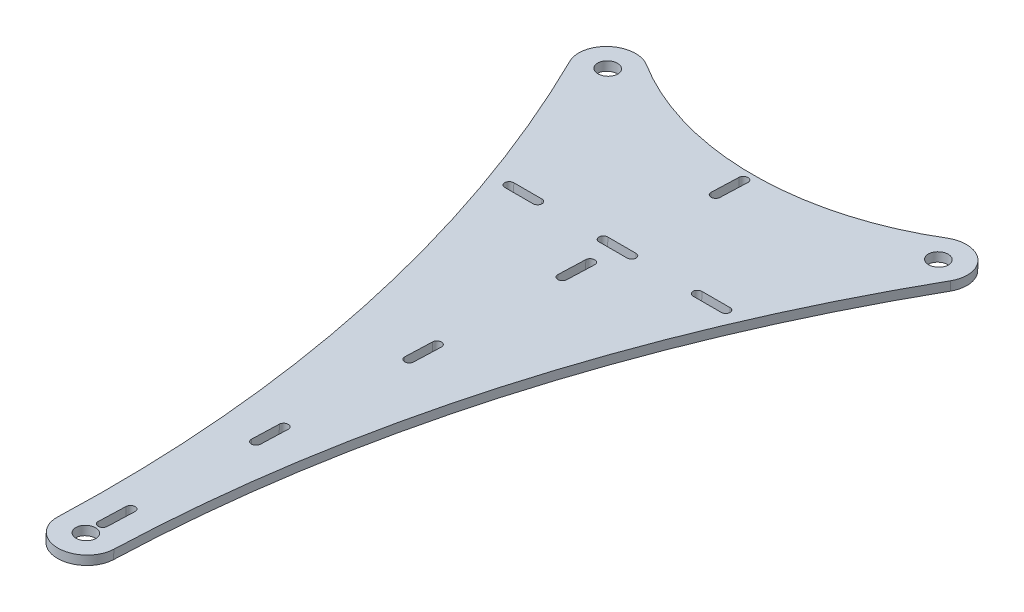
SolidWorks part; units mm, degrees
ref_plane "Front Plane" through (0, 0, 0) normal (0, 0, 1) x (1, 0, 0)
ref_plane "Top Plane" through (0, 0, 0) normal (0, 1, 0) x (1, 0, 0)
ref_plane "Right Plane" through (0, 0, 0) normal (1, 0, 0) x (0, 0, -1)
sketch "Sketch1" plane through (0, 79.1663, -2.7669) normal (0, -0.9994, 0.0349) x (0, -0.0349, -0.9994)
  line L0 (4.8479, 0) -> (-4.8479, 0) construction
  circle A0 centre (-118.8704, 0) radius 3.5
  circle A1 centre (126.4846, -59) radius 3.5
  circle A2 centre (126.4846, 59) radius 3.5
  circle A3 centre (-118.8704, 0) radius 10
  circle A4 centre (126.4846, -59) radius 10
  circle A5 centre (126.4846, 59) radius 10
  arc A6 (134.9245, 53.6364) -> (134.9245, -53.6364) centre (219.3232, 0) ccw
  arc A7 (121.9382, -67.9067) -> (-118.8704, -10) centre (-118.8704, -539.6619) ccw
  arc A8 (121.9382, 67.9067) -> (-118.8704, 10) centre (-118.8704, 539.6619) cw
  ellipse E0 centre (-118.8704, 0) end of major axis (-118.8704, 3.225) minor radius 3.223 construction
  ellipse E3 centre (126.9846, -59) end of major axis (126.9846, -56.075) minor radius 2.9032 construction
  point P16 (126.9846, -59)
  dimension "D1" = 7
  dimension "D3" = 7
  dimension "D4" = 20
  dimension "D5" = 100
  dimension "D2" = 0.5
extrude "Boss-Extrude1" add sketch "Sketch1" along normal blind 3.175 contours A5 A8 A3 A7 A4 A6 | A3 A0 | A5 A2 | A4 A1 region at (-6.8711, 83.0783, 109.1641) region at (0, 77.6526, -46.0785) region at (67.2871, 74.5711, -134.2454) region at (-52.4599, 74.9994, -121.9919)
sketch "Sketch2" plane through (0, 75.9932, -2.656) normal (0, -0.9994, 0.0349) x (1, 0, 0)
  line L0 (0, 112.8704) -> (0, 102.8704) construction
  line L1 (1.5875, 112.8704) -> (-1.5875, 112.8704) construction
  line L2 (1.5875, 102.8704) -> (-1.5875, 102.8704) construction
  line L3 (1.5875, 112.8704) -> (1.5875, 102.8704)
  line L4 (-1.5875, 112.8704) -> (-1.5875, 102.8704)
  line L5 (0, -105.9382) -> (0, -115.9382) construction
  line L6 (1.5875, -105.9382) -> (-1.5875, -105.9382) construction
  line L7 (1.5875, -115.9382) -> (-1.5875, -115.9382) construction
  line L8 (1.5875, -105.9382) -> (1.5875, -115.9382)
  line L9 (-1.5875, -105.9382) -> (-1.5875, -115.9382)
  line L10 (0, 58.1683) -> (0, 48.1683) construction
  line L11 (1.5875, 58.1683) -> (1.5875, 48.1683)
  line L12 (-1.5875, 58.1683) -> (-1.5875, 48.1683)
  line L13 (0, 3.4661) -> (0, -6.5339) construction
  line L14 (1.5875, 3.4661) -> (1.5875, -6.5339)
  line L15 (-1.5875, 3.4661) -> (-1.5875, -6.5339)
  line L16 (0, -51.236) -> (0, -61.236) construction
  line L17 (1.5875, -51.236) -> (1.5875, -61.236)
  line L18 (-1.5875, -51.236) -> (-1.5875, -61.236)
  line L19 (1.5875, -6.5339) -> (-1.5875, -6.5339) construction
  line L20 (38.5715, -70.9382) -> (28.5715, -70.9382) construction
  line L21 (38.5715, -72.5257) -> (38.5715, -69.3507) construction
  line L22 (28.5715, -72.5257) -> (28.5715, -69.3507) construction
  line L23 (38.5715, -72.5257) -> (28.5715, -72.5257)
  line L24 (38.5715, -69.3507) -> (28.5715, -69.3507)
  line L25 (5, -70.9382) -> (-5, -70.9382) construction
  line L26 (5, -72.5257) -> (5, -69.3507) construction
  line L27 (-5, -72.5257) -> (-5, -69.3507) construction
  line L28 (5, -72.5257) -> (-5, -72.5257)
  line L29 (5, -69.3507) -> (-5, -69.3507)
  line L30 (-28.5715, -70.9382) -> (-38.5715, -70.9382) construction
  line L31 (-28.5715, -72.5257) -> (-28.5715, -69.3507) construction
  line L32 (-38.5715, -72.5257) -> (-38.5715, -69.3507) construction
  line L33 (-28.5715, -72.5257) -> (-38.5715, -72.5257)
  line L34 (-28.5715, -69.3507) -> (-38.5715, -69.3507)
  arc A0 (1.5875, 112.8704) -> (-1.5875, 112.8704) centre (0, 112.8704) ccw
  arc A1 (-1.5875, 102.8704) -> (1.5875, 102.8704) centre (0, 102.8704) ccw
  arc A2 (1.5875, -105.9382) -> (-1.5875, -105.9382) centre (0, -105.9382) ccw
  arc A3 (-1.5875, -115.9382) -> (1.5875, -115.9382) centre (0, -115.9382) ccw
  arc A4 (1.5875, 58.1683) -> (-1.5875, 58.1683) centre (0, 58.1683) ccw
  arc A5 (-1.5875, 48.1683) -> (1.5875, 48.1683) centre (0, 48.1683) ccw
  arc A6 (1.5875, 3.4661) -> (-1.5875, 3.4661) centre (0, 3.4661) ccw
  arc A7 (-1.5875, -6.5339) -> (1.5875, -6.5339) centre (0, -6.5339) ccw
  arc A8 (1.5875, -51.236) -> (-1.5875, -51.236) centre (0, -51.236) ccw
  arc A9 (-1.5875, -61.236) -> (1.5875, -61.236) centre (0, -61.236) ccw
  arc A10 (38.5715, -72.5257) -> (38.5715, -69.3507) centre (38.5715, -70.9382) ccw
  arc A11 (28.5715, -69.3507) -> (28.5715, -72.5257) centre (28.5715, -70.9382) ccw
  arc A12 (5, -72.5257) -> (5, -69.3507) centre (5, -70.9382) ccw
  arc A13 (-5, -69.3507) -> (-5, -72.5257) centre (-5, -70.9382) ccw
  arc A14 (-28.5715, -72.5257) -> (-28.5715, -69.3507) centre (-28.5715, -70.9382) ccw
  arc A15 (-38.5715, -69.3507) -> (-38.5715, -72.5257) centre (-38.5715, -70.9382) ccw
  point P6 (0, 107.8704)
  point P11 (0, -110.9382)
  point P22 (33.5715, -70.9382)
  point P28 (0, 53.1683)
  point P35 (0, -1.5339)
  point P42 (0, -56.236)
  point P59 (0, -70.9382)
  point P70 (-33.5715, -70.9382)
  dimension "D1" = 4
extrude "Cut-Extrude1" cut sketch "Sketch2" against normal blind 3.175
